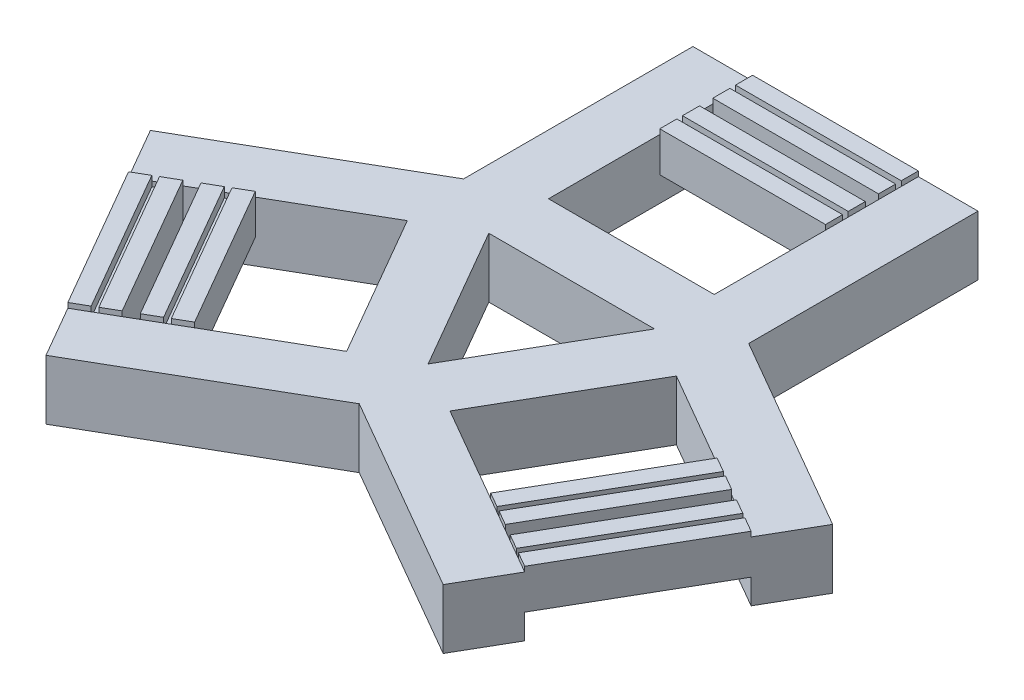
SolidWorks part; units mm, degrees
ref_plane "Alzado" through (0, 0, 0) normal (0, 0, 1) x (1, 0, 0)
ref_plane "Planta" through (0, 0, 0) normal (0, 1, 0) x (1, 0, 0)
ref_plane "Vista lateral" through (0, 0, 0) normal (1, 0, 0) x (0, 0, -1)
sketch "Croquis3" plane through (0, 0, 0) normal (1, 0, 0) x (0, 0, -1)
  line L0 (0, -1000) -> (0, 49000) construction
sketch "Croquis1" plane through (0, 0, 0) normal (0, 1, 0) x (1, 0, 0)
  line L0 (0, 0) -> (0, 360) construction
  line L1 (0, 0) -> (-311.7691, -180) construction
  line L2 (0, 0) -> (311.7691, -180) construction
  line L7 (-374.2691, -71.7468) -> (-249.2691, -288.2532) construction
  line L12 (-311.7691, -180) -> (-381.0512, -220)
  line L13 (-443.5512, -111.7468) -> (-318.5512, -328.2532) construction
  line L14 (-125, 360) -> (125, 360) construction
  line L15 (249.2691, -288.2532) -> (374.2691, -71.7468) construction
  line L16 (0, 360) -> (0, 440)
  line L17 (311.7691, -180) -> (381.0512, -220)
  line L18 (318.5512, -328.2532) -> (443.5512, -111.7468) construction
  line L19 (-125, 440) -> (125, 440) construction
  line L20 (-125, 440) -> (-125, 72.1688)
  line L21 (-125, 72.1688) -> (-443.5512, -111.7468)
  line L23 (125, 440) -> (125, 72.1688)
  line L24 (125, 72.1688) -> (443.5512, -111.7468)
  line L25 (318.5512, -328.2532) -> (0, -144.3376)
  line L26 (0, -144.3376) -> (-318.5512, -328.2532)
  line L27 (-443.5512, -111.7468) -> (-469.5319, -126.7468)
  line L28 (-318.5512, -328.2532) -> (-344.5319, -343.2532)
  line L29 (-344.5319, -343.2532) -> (-469.5319, -126.7468)
  line L30 (-292.5704, -313.2532) -> (-417.5704, -96.7468)
  line L31 (-223.2884, -273.2532) -> (-348.2884, -56.7468)
  line L32 (-275.2499, -303.2532) -> (-400.2499, -86.7468)
  line L33 (-439.8706, -109.6218) -> (-314.8706, -326.1282)
  line L34 (-447.2318, -113.8718) -> (-322.2318, -330.3782)
  line L35 (-370.5885, -69.6218) -> (-245.5885, -286.1282)
  line L36 (-377.9498, -73.8718) -> (-252.9498, -290.3782)
  line L37 (-125, 470) -> (125, 470)
  line L38 (125, 444.25) -> (-125, 444.25)
  line L39 (125, 435.75) -> (-125, 435.75)
  line L40 (-125, 410) -> (125, 410)
  line L41 (-125, 390) -> (125, 390)
  line L42 (125, 364.25) -> (-125, 364.25)
  line L43 (125, 355.75) -> (-125, 355.75)
  line L44 (-125, 330) -> (125, 330)
  line L45 (469.5319, -126.7468) -> (344.5319, -343.2532)
  line L46 (322.2318, -330.3782) -> (447.2318, -113.8718)
  line L47 (314.8706, -326.1282) -> (439.8706, -109.6218)
  line L48 (417.5704, -96.7468) -> (292.5704, -313.2532)
  line L49 (400.2499, -86.7468) -> (275.2499, -303.2532)
  line L50 (252.9498, -290.3782) -> (377.9498, -73.8718)
  line L51 (245.5885, -286.1282) -> (370.5885, -69.6218)
  line L52 (348.2884, -56.7468) -> (223.2884, -273.2532)
  line L53 (-125, 440) -> (-125, 470)
  line L54 (125, 440) -> (125, 470)
  line L55 (318.5512, -328.2532) -> (344.5319, -343.2532)
  line L56 (469.5319, -126.7468) -> (443.5512, -111.7468)
  line L57 (-125, 72.1688) -> (125, 72.1688)
  line L58 (-125, 72.1688) -> (0, -144.3376)
  line L59 (125, 72.1688) -> (0, -144.3376)
  line L60 (-202.9423, 27.1688) -> (-77.9423, -189.3376)
  line L61 (77.9423, -189.3376) -> (202.9423, 27.1688)
  line L62 (-125, 162.1688) -> (125, 162.1688)
  line L63 (-215, 440) -> (-215, 470)
  line L64 (-215, 440) -> (-215, 124.1303)
  line L65 (-215, 124.1303) -> (-488.5512, -33.8045)
  line L66 (-488.5512, -33.8045) -> (-514.5319, -48.8045)
  line L67 (488.5512, -33.8045) -> (215, 124.1303)
  line L68 (215, 124.1303) -> (215, 440)
  line L69 (215, 440) -> (215, 470)
  line L70 (488.5512, -33.8045) -> (514.5319, -48.8045)
  line L71 (-273.5512, -406.1955) -> (0, -248.2606)
  line L72 (0, -248.2606) -> (273.5512, -406.1955)
  line L73 (273.5512, -406.1955) -> (299.5319, -421.1955)
  line L74 (-273.5512, -406.1955) -> (-299.5319, -421.1955)
  line L75 (-299.5319, -421.1955) -> (-344.5319, -343.2532)
  line L76 (299.5319, -421.1955) -> (344.5319, -343.2532)
  line L77 (514.5319, -48.8045) -> (469.5319, -126.7468)
  line L78 (-469.5319, -126.7468) -> (-514.5319, -48.8045)
  line L79 (-125, 470) -> (-215, 470)
  line L80 (215, 470) -> (125, 470)
  circle A1 centre (0, 0) radius 400 construction
  point P8 (0, 360)
  point P9 (-311.7691, -180)
  point P14 (-381.0512, -220)
  point P16 (0, 360)
  point P20 (311.7691, -180)
  point P22 (0, 400)
  point P25 (381.0512, -220)
  point P28 (0, 440)
  point P32 (-346.4102, -200)
  point P34 (346.4102, -200)
  point P85 (0, 0)
  point P107 (0, 0)
  dimension "D1" = 250
  dimension "D9" = 800
  dimension "D2" = 120
  dimension "D3" = 120
  dimension "D4" = 80
  dimension "D5" = 80
  dimension "D6" = 80
  dimension "D7" = 250
  dimension "D8" = 250
  dimension "D10" = 30
  dimension "D11" = 60
  dimension "D12" = 8.5
  dimension "D13" = 8.5
  dimension "D15" = 90
  dimension "D16" = 90
  dimension "D17" = 90
  dimension "D18" = 90
  dimension "D14" = 3
  dimension "D19" = 3
extrude "Saliente-Extruir1" add sketch "Croquis1" along normal mid plane 30 contours L21 L36 L26 L35 | L27 L34 L28 L26 L33 L21 | L46 L56 L24 L47 L25 L55 | L51 L25 L50 L24 | L43 L23 L42 L20 | L23 L54 L38 L53 L20 L39 region at (-344.4706, 0, 126.7114) region at (-348.3497, 0, 273.2886) region at (-122.4986, 0, -360) region at (310.3177, 0, 179.162) region at (-122.4986, 0, -437.875) region at (348.3497, 0, 273.2886)
extrude "Saliente-Extruir2" add sketch "Croquis1<4>" along normal mid plane 60 contours L16 L40 L23 L39 | L38 L54 L37 L53 | L20 L40 L16 L39 | L42 L16 L41 L20 | L42 L23 L41 L16 | L20 L44 L23 L43 | L34 L27 L29 L28 | L12 L33 L26 L30 | L21 L33 L12 L30 | L36 L21 L32 L12 | L21 L35 L26 L31 | L36 L12 L32 L26 | L24 L52 L25 L51 | L50 L25 L49 L17 | L50 L17 L49 L24 | L24 L48 L17 L47 | L17 L48 L25 L47 | L45 L56 L46 L55 region at (-295.3498, 0, 242.6891) region at (-357.8498, 0, 134.4359) region at (-334.9705, 0, 265.5641) region at (-397.4705, 0, 157.3109) region at (-296.9385, 0, 171.4375) region at (-395.8819, 0, 228.5625) region at (0, 0, -342.875) region at (296.9385, 0, 171.4375) region at (-62.5, 0, -377.125) region at (295.3498, 0, 242.6891) region at (62.5, 0, -377.125) region at (357.8498, 0, 134.4359) region at (-62.5, 0, -422.875) region at (334.9705, 0, 265.5641) region at (62.5, 0, -422.875) region at (397.4705, 0, 157.3109) region at (0, 0, -457.125) region at (395.8819, 0, 228.5625)
sketch "Croquis1<4>" plane through (0, 0, 0) normal (0, 1, 0) x (1, 0, 0) same geometry as "Croquis1"
extrude "Saliente-Extruir3" add sketch "Croquis1<5>" along normal blind 22.5 contours L53 L79 L63 L64 L65 L66 L78 L27 L21 L20 | L62 L20 L57 L23 | L21 L60 L26 L58 | L25 L61 L24 L59 | L69 L80 L54 L23 L24 L56 L77 L70 L67 L68 | L73 L76 L55 L25 L26 L28 L75 L74 L71 L72 region at (-392.663, 0, 74.1378) region at (-245.5561, 0, 294.6843) region at (-101.4711, 0, 58.5844) region at (0, 0, -117.1688) region at (101.4711, 0, 58.5844) region at (132.1263, 0, -117.1688)
sketch "Croquis1<5>" plane through (0, 0, 0) normal (0, 1, 0) x (1, 0, 0) same geometry as "Croquis1"
extrude "Saliente-Extruir4" add sketch "Croquis1<6>" against normal blind 67.5 contours L53 L79 L63 L64 L65 L66 L78 L27 L21 L20 | L21 L60 L26 L58 | L62 L20 L57 L23 | L69 L80 L54 L23 L24 L56 L77 L70 L67 L68 | L25 L61 L24 L59 | L73 L76 L55 L25 L26 L28 L75 L74 L71 L72 region at (-392.663, 0, 74.1378) region at (-245.5561, 0, 294.6843) region at (-101.4711, 0, 58.5844) region at (0, 0, -117.1688) region at (101.4711, 0, 58.5844) region at (132.1263, 0, -117.1688)
sketch "Croquis1<6>" plane through (0, 0, 0) normal (0, 1, 0) x (1, 0, 0) same geometry as "Croquis1"
sketch "Croquis5" plane through (0, 22.5, 0) normal (0, 1, 0) x (1, 0, 0)
  line L0 (-202.9423, 27.1688) -> (-125, 72.1688)
  line L1 (-125, 72.1688) -> (-125, 162.1688)
  line L2 (-125, 72.1688) -> (-215, 124.1303)
  line L3 (125, 162.1688) -> (125, 72.1688)
  line L4 (125, 72.1688) -> (202.9423, 27.1688)
  line L5 (215, 124.1303) -> (125, 72.1688)
  line L6 (-77.9423, -189.3376) -> (0, -144.3376)
  line L7 (0, -144.3376) -> (77.9423, -189.3376)
  line L8 (0, -144.3376) -> (0, -248.2606)
